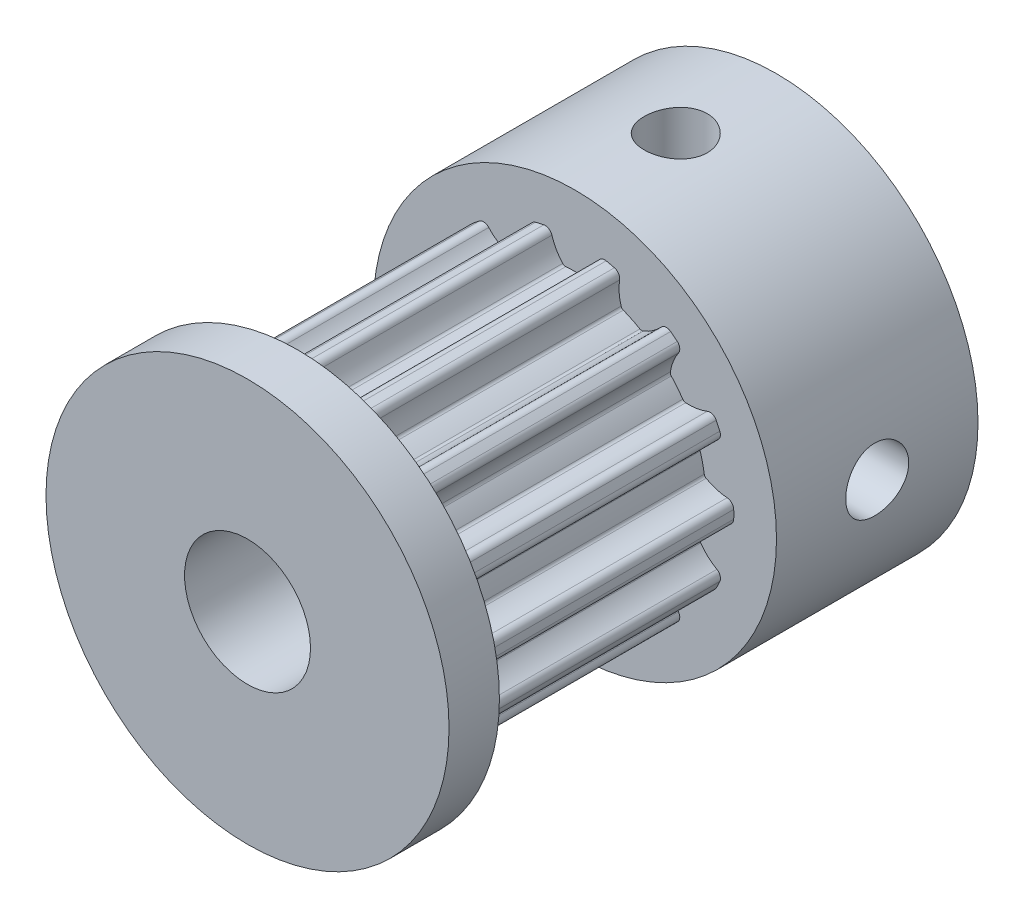
SolidWorks part; units mm, degrees
material "6061-T6 (SS)"
ref_plane "前基準面" through (0, 0, 0) normal (0, 0, 1) x (1, 0, 0)
ref_plane "上基準面" through (0, 0, 0) normal (0, 1, 0) x (1, 0, 0)
ref_plane "右基準面" through (0, 0, 0) normal (1, 0, 0) x (0, 0, -1)
sketch "草圖1" plane through (0, 0, 0) normal (0, 0, 1) x (1, 0, 0)
  circle A0 centre (0, 0) radius 6.305
  dimension "D1" = 12.61
extrude "填料-伸長1" add sketch "草圖1" along normal mid plane 11
sketch "草圖2" plane through (0, 0, 5.5) normal (0, 0, 1) x (1, 0, 0)
  line L0 (0, 0) -> (0, 6.559) construction
  line L1 (-0.975, 6.559) -> (0.975, 6.559) construction
  arc A0 (-0.3652, 5.1821) -> (0.3652, 5.1821) centre (0, 0) cw
  circle A1 centre (0, 0) radius 6.305 construction
  arc A2 (-1.2389, 6.1821) -> (-0.9158, 5.9884) centre (-1.1839, 5.9075) cw
  arc A3 (-0.9158, 5.9884) -> (-0.4868, 5.2309) centre (0.975, 6.559) ccw
  arc A4 (-0.4868, 5.2309) -> (-0.3652, 5.1821) centre (-0.3758, 5.3318) ccw
  arc A5 (0.4868, 5.2309) -> (0.3652, 5.1821) centre (0.3758, 5.3318) cw
  arc A6 (0.9158, 5.9884) -> (0.4868, 5.2309) centre (-0.975, 6.559) cw
  arc A7 (1.2389, 6.1821) -> (0.9158, 5.9884) centre (1.1839, 5.9075) ccw
  point P6 (0, 5.195)
  point P18 (0, 6.305)
  dimension "D1" = 1.11
  dimension "D2" = 0.15
  dimension "D3" = 1.975
  dimension "D4" = 0.28
  dimension "D5" = 1.95
  dimension "D6" = 0.254
extrude "除料-伸長1" cut sketch "草圖2" against normal through all and the other way through all flip side to cut
pattern_circular "環狀複製排列1" count 14 over 360 about axis through (0, 0, 5.5) along (0, 0, 1) of "除料-伸長1"
sketch "草圖3" plane through (0, 0, 5.5) normal (0, 0, 1) x (1, 0, 0)
  circle A0 centre (0, 0) radius 8
  dimension "D1" = 16
extrude "填料-伸長2" add sketch "草圖3" along normal blind 2
sketch "草圖5" plane through (0, 0, -5.5) normal (0, 0, -1) x (-1, 0, 0)
  circle A0 centre (0, 0) radius 8
  circle A1 centre (0, 0) radius 8 construction
extrude "填料-伸長3" add sketch "草圖5" along normal blind 8
sketch "草圖4" plane through (0, 0, 7.5) normal (0, 0, 1) x (1, 0, 0)
  circle A0 centre (0, 0) radius 2.5
  dimension "D1" = 5
extrude "除料-伸長2" cut sketch "草圖4" against normal through all
hole_wizard "M3x0.5 螺紋孔1" positions "草圖6" profile "草圖7" tap size "M3x0.5" standard "Ansi Metric" end condition through all
sketch "草圖6" plane through (0, 0, 0) normal (0, 1, 0) x (1, 0, 0)
  line L0 (0, 13.5) -> (0, 5.5) construction
  line L1 (2.5, 13.5) -> (-2.5, 13.5) construction
  line L2 (-0.3652, 5.5) -> (0.3652, 5.5) construction
  point P0 (0, 9.5)
sketch "草圖7" plane through (0, 0, -9.5) normal (1, 0, 0) x (0, 0, -1)
  line L0 (0, 0) -> (0, 8)
  line L1 (0, 8) -> (1.25, 8)
  line L2 (1.25, 8) -> (1.25, 0)
  line L5 (1.25, 0) -> (0, 0)
  line L11 (0, -6.35) -> (0, 107.95) construction
  dimension "貫穿螺孔鑽直徑" = 2.5
  dimension "貫穿螺孔鑽深度" = 8
pattern_circular "環狀複製排列2" count 2 every 90 about axis through (0, 0, -13.5) along (0, 0, -1) of "M3x0.5 螺紋孔1"
